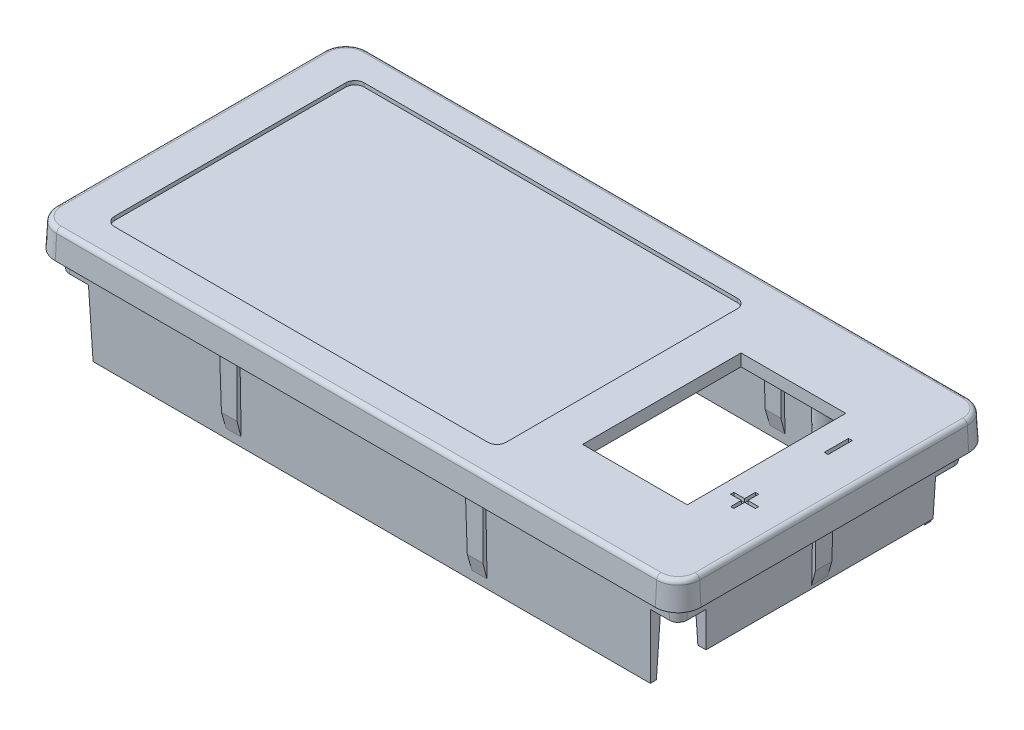
SolidWorks part; units mm, degrees
material "ABS PC"
ref_plane "Front" through (0, 0, 0) normal (0, 0, 1) x (1, 0, 0)
ref_plane "Top" through (0, 0, 0) normal (0, 1, 0) x (1, 0, 0)
ref_plane "Right" through (0, 0, 0) normal (1, 0, 0) x (0, 0, -1)
sketch "Sketch1" plane through (0, 0, 0) normal (0, 1, 0) x (1, 0, 0)
  line L1 (-32.95, -17.2) -> (32.95, -17.2)
  line L2 (-35.45, -14.7) -> (-35.45, 14.7)
  line L3 (-32.95, 17.2) -> (32.95, 17.2)
  line L4 (35.45, -14.7) -> (35.45, 14.7)
  line L5 (-35.45, -17.2) -> (35.45, 17.2) construction
  line L6 (-35.45, 17.2) -> (35.45, -17.2) construction
  arc A0 (32.95, -17.2) -> (35.45, -14.7) centre (32.95, -14.7) ccw
  arc A1 (-35.45, 14.7) -> (-32.95, 17.2) centre (-32.95, 14.7) cw
  arc A2 (-32.95, -17.2) -> (-35.45, -14.7) centre (-32.95, -14.7) cw
  arc A3 (32.95, 17.2) -> (35.45, 14.7) centre (32.95, 14.7) cw
  point P0 (0, 0)
  dimension "D3" = 2.5
  dimension "D1" = 70.9
  dimension "D2" = 34.4
extrude "Boss-Extrude1" add sketch "Sketch1" along normal blind 3 draft 3
fillet "Fillet1" radius 0.5 8 edges at (0, 3, 17.0428) (-34.6066, 3, 16.3566) (-35.2928, 3, 0) (-34.6066, 3, -16.3566) (0, 3, -17.0428) (34.6066, 3, -16.3566) (35.2928, 3, 0) (34.6066, 3, 16.3566)
sketch "Sketch2" plane through (0, 0, 0) normal (0, -1, 0) x (1, 0, 0)
  line L8 (32.95, 16.45) -> (-32.95, 16.45)
  line L9 (-34.7, 14.7) -> (-34.7, -14.7)
  line L10 (-32.95, -16.45) -> (32.95, -16.45)
  line L11 (34.7, -14.7) -> (34.7, 14.7)
  line L12 (32.95, 16.45) -> (-32.95, 16.45)
  line L13 (-34.7, 14.7) -> (-34.7, -14.7)
  line L14 (-32.95, -16.45) -> (32.95, -16.45)
  line L15 (34.7, -14.7) -> (34.7, 14.7)
  arc A8 (34.7, 14.7) -> (32.95, 16.45) centre (32.95, 14.7) ccw
  arc A9 (-32.95, 16.45) -> (-34.7, 14.7) centre (-32.95, 14.7) ccw
  arc A10 (-34.7, -14.7) -> (-32.95, -16.45) centre (-32.95, -14.7) ccw
  arc A11 (32.95, -16.45) -> (34.7, -14.7) centre (32.95, -14.7) ccw
  arc A12 (34.7, 14.7) -> (32.95, 16.45) centre (32.95, 14.7) ccw
  arc A13 (-32.95, 16.45) -> (-34.7, 14.7) centre (-32.95, 14.7) ccw
  arc A14 (-34.7, -14.7) -> (-32.95, -16.45) centre (-32.95, -14.7) ccw
  arc A15 (32.95, -16.45) -> (34.7, -14.7) centre (32.95, -14.7) ccw
  dimension "D1" = 0.75
extrude "Cut-Extrude1" cut sketch "Sketch2" against normal blind 0.5
sketch "Sketch4" plane through (0, 0.5, 0) normal (0, -1, 0) x (1, 0, 0)
  line L1 (31.65, -14.4) -> (-31.65, -14.4)
  line L2 (32.65, -13.4) -> (32.65, 13.4)
  line L3 (31.65, 14.4) -> (-31.65, 14.4)
  line L4 (-32.65, -13.4) -> (-32.65, 13.4)
  line L5 (32.65, -14.4) -> (-32.65, 14.4) construction
  line L6 (32.65, 14.4) -> (-32.65, -14.4) construction
  line L8 (32.95, 15.75) -> (-32.95, 15.75)
  line L9 (-34, 14.7) -> (-34, -14.7)
  line L10 (-32.95, -15.75) -> (32.95, -15.75)
  line L11 (34, -14.7) -> (34, 14.7)
  line L12 (32.95, 15.75) -> (-32.95, 15.75)
  line L13 (-34, 14.7) -> (-34, -14.7)
  line L14 (-32.95, -15.75) -> (32.95, -15.75)
  line L15 (34, -14.7) -> (34, 14.7)
  arc A0 (32.65, 13.4) -> (31.65, 14.4) centre (31.65, 13.4) ccw
  arc A1 (31.65, -14.4) -> (32.65, -13.4) centre (31.65, -13.4) ccw
  arc A2 (-31.65, -14.4) -> (-32.65, -13.4) centre (-31.65, -13.4) cw
  arc A3 (-31.65, 14.4) -> (-32.65, 13.4) centre (-31.65, 13.4) ccw
  arc A8 (34, 14.7) -> (32.95, 15.75) centre (32.95, 14.7) ccw
  arc A9 (-32.95, 15.75) -> (-34, 14.7) centre (-32.95, 14.7) ccw
  arc A10 (-34, -14.7) -> (-32.95, -15.75) centre (-32.95, -14.7) ccw
  arc A11 (32.95, -15.75) -> (34, -14.7) centre (32.95, -14.7) ccw
  arc A12 (34, 14.7) -> (32.95, 15.75) centre (32.95, 14.7) ccw
  arc A13 (-32.95, 15.75) -> (-34, 14.7) centre (-32.95, 14.7) ccw
  arc A14 (-34, -14.7) -> (-32.95, -15.75) centre (-32.95, -14.7) ccw
  arc A15 (32.95, -15.75) -> (34, -14.7) centre (32.95, -14.7) ccw
  point P0 (0, 0)
  dimension "D4" = 1
  dimension "D2" = 1.35
  dimension "D3" = 1.35
  dimension "D1" = 0.7
extrude "Boss-Extrude2" add sketch "Sketch4" along normal offset from surface 12.3 draft 2
sketch "Sketch5" plane through (0, 0.5, 0) normal (0, -1, 0) x (1, 0, 0)
  line L4 (31.65, 14.4) -> (-31.65, 14.4)
  line L5 (-32.65, 13.4) -> (-32.65, -13.4)
  line L6 (-31.65, -14.4) -> (31.65, -14.4)
  line L7 (32.65, -13.4) -> (32.65, 13.4)
  line L8 (31.65, 14.4) -> (-31.65, 14.4)
  line L9 (-32.65, 13.4) -> (-32.65, -13.4)
  line L10 (-31.65, -14.4) -> (31.65, -14.4)
  line L11 (32.65, -13.4) -> (32.65, 13.4)
  arc A4 (-31.65, 14.4) -> (-32.65, 13.4) centre (-31.65, 13.4) ccw
  arc A5 (-32.65, -13.4) -> (-31.65, -14.4) centre (-31.65, -13.4) ccw
  arc A6 (31.65, -14.4) -> (32.65, -13.4) centre (31.65, -13.4) ccw
  arc A7 (32.65, 13.4) -> (31.65, 14.4) centre (31.65, 13.4) ccw
  arc A8 (-31.65, 14.4) -> (-32.65, 13.4) centre (-31.65, 13.4) ccw
  arc A9 (-32.65, -13.4) -> (-31.65, -14.4) centre (-31.65, -13.4) ccw
  arc A10 (31.65, -14.4) -> (32.65, -13.4) centre (31.65, -13.4) ccw
  arc A11 (32.65, 13.4) -> (31.65, 14.4) centre (31.65, 13.4) ccw
  dimension "D1" = 0
extrude "Cut-Extrude2" cut sketch "Sketch5" against normal blind 1.2 draft 2
sketch "Sketch7" plane through (0, -9.3, 0) normal (0, -1, 0) x (1, 0, 0)
  line L1 (40, -13.25) -> (-40, -13.25)
  line L2 (40, -13.25) -> (40, 13.25)
  line L3 (40, 13.25) -> (-40, 13.25)
  line L4 (-40, -13.25) -> (-40, 13.25)
  line L5 (40, -13.25) -> (-40, 13.25) construction
  line L6 (40, 13.25) -> (-40, -13.25) construction
  point P0 (0, 0)
  dimension "D1" = 26.5
  dimension "D2" = 80
extrude "Cut-Extrude3" cut sketch "Sketch7" against normal offset from surface (3.3 mm away) 9 up to face at (0, 3, 0)
sketch "Sketch6" plane through (0, -9.3, 0) normal (0, -1, 0) x (1, 0, 0)
  line L0 (0, 25.2339) -> (0, -25.4955) construction
  line L1 (-36.3009, 18.0509) -> (-30.6, 18.0509)
  line L2 (-36.3009, 18.0509) -> (-36.3009, 12.35)
  line L3 (-36.3009, 12.35) -> (-30.6, 12.35)
  line L4 (-30.6, 18.0509) -> (-30.6, 12.35)
  line L5 (-36.3009, 18.0509) -> (-30.6, 12.35) construction
  line L6 (-36.3009, 12.35) -> (-30.6, 18.0509) construction
  line L7 (-41.5983, 0) -> (43.5606, 0) construction
  line L8 (36.3009, 12.35) -> (30.6, 18.0509) construction
  line L9 (36.3009, 18.0509) -> (30.6, 12.35) construction
  line L10 (30.6, 18.0509) -> (30.6, 12.35)
  line L11 (36.3009, 12.35) -> (30.6, 12.35)
  line L12 (36.3009, 18.0509) -> (36.3009, 12.35)
  line L13 (36.3009, 18.0509) -> (30.6, 18.0509)
  line L14 (36.3009, -18.0509) -> (30.6, -12.35) construction
  line L15 (36.3009, -12.35) -> (30.6, -18.0509) construction
  line L16 (-36.3009, -12.35) -> (-30.6, -18.0509) construction
  line L17 (-36.3009, -18.0509) -> (-30.6, -12.35) construction
  line L18 (36.3009, -18.0509) -> (30.6, -18.0509)
  line L19 (36.3009, -18.0509) -> (36.3009, -12.35)
  line L20 (36.3009, -12.35) -> (30.6, -12.35)
  line L21 (30.6, -18.0509) -> (30.6, -12.35)
  line L22 (-30.6, -18.0509) -> (-30.6, -12.35)
  line L23 (-36.3009, -12.35) -> (-30.6, -12.35)
  line L24 (-36.3009, -18.0509) -> (-36.3009, -12.35)
  line L25 (-36.3009, -18.0509) -> (-30.6, -18.0509)
  arc A0 (-32.95, 15.4078) -> (-33.6578, 14.7) centre (-32.95, 14.7) ccw construction
  point P0 (-33.4505, 15.2005)
  point P14 (33.4505, 15.2005)
  point P23 (33.4505, -15.2005)
  point P24 (-33.4505, -15.2005)
  dimension "D1" = 61.2
extrude "Cut-Extrude4" cut sketch "Sketch6" against normal offset from surface 5 draft 2
sketch "Sketch8" plane through (0, -9.3, 0) normal (0, -1, 0) x (1, 0, 0)
  line L0 (-30.6, -15.4078) -> (-30.6, -14.7422) construction
  line L1 (-26.8, -14.0722) -> (5.2, -14.0722)
  line L2 (-26.8, -14.0722) -> (-26.8, -16.0722)
  line L3 (-26.8, -16.0722) -> (5.2, -16.0722)
  line L4 (5.2, -14.0722) -> (5.2, -16.0722)
  line L5 (-26.8, -14.0722) -> (5.2, -16.0722) construction
  line L6 (-26.8, -16.0722) -> (5.2, -14.0722) construction
  line L8 (30.6, -14.7422) -> (-30.6, -14.7422) construction
  point P0 (-10.8, -15.0722)
  dimension "D1" = 3.8
  dimension "D2" = 32
  dimension "D3" = 2
  dimension "D4" = 0.33
extrude "Cut-Extrude5" cut sketch "Sketch8" against normal up to surface (7.3 mm away) up to face at (-32.5043, -2, -14.2543)
fillet "Fillet3" radius 0.5 8 edges at (32.3275, 1.7, 14.0775) (32.6081, 1.7, 0) (32.3275, 1.7, -14.0775) (0, 1.7, -14.3581) (-32.3275, 1.7, -14.0775) (-32.6081, 1.7, 0) (-32.3275, 1.7, 14.0775) (0, 1.7, 14.3581)
sketch "Sketch9" plane through (0, 1.7, 0) normal (0, -1, 0) x (1, 0, 0)
  line L0 (-32.1253, 13.4) -> (-32.1253, -13.4) construction
  line L2 (31.65, 13.8753) -> (-31.65, 13.8753) construction
  line L3 (0, 20.8963) -> (0, -22.9898) construction
  line L4 (48.011, 0) -> (-42.4283, 0) construction
  circle A0 centre (-30.6253, 12.3753) radius 1.5
  circle A4 centre (-30.6253, 12.3753) radius 0.8
  circle A5 centre (30.6253, 12.3753) radius 0.8
  circle A6 centre (30.6253, 12.3753) radius 1.5
  circle A7 centre (30.6253, -12.3753) radius 1.5
  circle A8 centre (30.6253, -12.3753) radius 0.8
  circle A9 centre (-30.6253, -12.3753) radius 0.8
  circle A10 centre (-30.6253, -12.3753) radius 1.5
  dimension "D1" = 3
  dimension "D2" = 1.5
  dimension "D3" = 1.5
  dimension "D4" = 0.7
extrude "Boss-Extrude3" add sketch "Sketch9" along normal blind 0.6 draft 2
sketch "Sketch10" plane through (0, 1.7, 0) normal (0, -1, 0) x (1, 0, 0)
  line L0 (-32.877, 0) -> (32.877, 0) construction
  line L1 (-32.877, -12.4652) -> (-32.877, 12.4652) construction
  line L2 (32.877, 12.4652) -> (32.877, -12.4652) construction
  line L3 (35.45, 14.7) -> (35.45, -14.7) construction
  line L4 (-31.65, 14.3749) -> (31.65, 14.3749) construction
  line L5 (-32.6249, -13.4) -> (-32.6249, 13.4) construction
  circle A0 centre (21.95, 12.6249) radius 1.75
  circle A1 centre (21.95, -12.6249) radius 1.75
  circle A2 centre (-30.8749, 0) radius 1.75
  dimension "D2" = 3.5
  dimension "D4" = 1.75
  dimension "D1" = 13.5
  dimension "D3" = 1.75
extrude "Boss-Extrude4" add sketch "Sketch10" along normal blind 1 draft 2
sketch "Sketch11" plane through (0, 1.7, 0) normal (0, -1, 0) x (1, 0, 0)
  line L0 (35.45, 0) -> (-35.45, 0) construction
  line L1 (35.45, 14.7) -> (35.45, -14.7) construction
  line L2 (-35.45, -14.7) -> (-35.45, 14.7) construction
  circle A0 centre (21.95, 12.6249) radius 1.25
  circle A1 centre (21.95, 12.6249) radius 0.55
  circle A2 centre (21.95, -12.6249) radius 0.55
  circle A3 centre (21.95, -12.6249) radius 1.25
  circle A4 centre (-30.8749, 0) radius 1.25
  circle A5 centre (-30.8749, 0) radius 0.55
  dimension "D1" = 2.5
  dimension "D2" = 0.7
extrude "Boss-Extrude5" add sketch "Sketch11" along normal blind 6 draft 1
sketch "Sketch12" plane through (0, 3, 0) normal (0, 1, 0) x (1, 0, 0)
  line L0 (35.45, -14.7) -> (35.45, 14.7) construction
  line L1 (16.45, -8.7) -> (27.95, -8.7)
  line L2 (16.45, -8.7) -> (16.45, 8.7)
  line L3 (16.45, 8.7) -> (27.95, 8.7)
  line L4 (27.95, -8.7) -> (27.95, 8.7)
  line L5 (16.45, -8.7) -> (27.95, 8.7) construction
  line L6 (16.45, 8.7) -> (27.95, -8.7) construction
  line L9 (-32.95, -17.2) -> (32.95, -17.2) construction
  line L11 (32.95, 17.2) -> (-32.95, 17.2) construction
  point P0 (22.2, 0)
  dimension "D1" = 7.5
  dimension "D2" = 8.5
  dimension "D3" = 8.5
  dimension "D4" = 11.5
extrude "Cut-Extrude6" cut sketch "Sketch12" against normal through all draft 1
sketch "Sketch13" plane through (0, 3, 0) normal (0, 1, 0) x (1, 0, 0)
  line L0 (-35.45, 14.7) -> (-35.45, -14.7) construction
  line L1 (-29.95, -13.7) -> (11.05, -13.7)
  line L2 (-30.95, -12.7) -> (-30.95, 12.7)
  line L3 (-29.95, 13.7) -> (11.05, 13.7)
  line L4 (12.05, -12.7) -> (12.05, 12.7)
  line L5 (-30.95, -13.7) -> (12.05, 13.7) construction
  line L6 (-30.95, 13.7) -> (12.05, -13.7) construction
  line L7 (32.95, 17.2) -> (-32.95, 17.2) construction
  arc A0 (11.05, -13.7) -> (12.05, -12.7) centre (11.05, -12.7) ccw
  arc A1 (-30.95, 12.7) -> (-29.95, 13.7) centre (-29.95, 12.7) cw
  arc A2 (-29.95, -13.7) -> (-30.95, -12.7) centre (-29.95, -12.7) cw
  arc A3 (11.05, 13.7) -> (12.05, 12.7) centre (11.05, 12.7) cw
  point P0 (-9.45, 0)
  dimension "D4" = 1
  dimension "D1" = 4.5
  dimension "D2" = 3.5
  dimension "D3" = 43
extrude "Cut-Extrude7" cut sketch "Sketch13" against normal blind 0.4 draft 2
sketch "Sketch14" plane through (0, 3, 0) normal (0, 1, 0) x (1, 0, 0)
  line L0 (32.2274, 6.7344) -> (32.2274, 3.8531) construction
  line L1 (32.6557, -3.4671) -> (32.6557, -8.7237) construction
  text T0 "+" font "Century Gothic" height 4
  text T1 "-" font "Century Gothic" height 4
extrude "Cut-Extrude8" cut sketch "Sketch14" against normal blind 0.4 draft 1
sketch "Sketch16" plane through (0, 1.7, 0) normal (0, -1, 0) x (1, 0, 0)
  line L0 (-32.1253, 12.3753) -> (-32.1253, 1.2244) construction
  line L1 (-16.1253, 14.075) -> (-14.1253, 14.075)
  line L2 (-16.1253, 14.075) -> (-16.1253, 16.075)
  line L3 (-16.1253, 16.075) -> (-14.1253, 16.075)
  line L4 (-14.1253, 14.075) -> (-14.1253, 16.075)
  line L5 (-16.1253, 15.075) -> (-30.6, 15.075) construction
  line L6 (-30.6, 14.7422) -> (-30.6, 15.4078) construction
  line L7 (10.8747, 14.075) -> (12.8747, 14.075)
  line L8 (10.8747, 14.075) -> (10.8747, 16.075)
  line L9 (10.8747, 16.075) -> (12.8747, 16.075)
  line L10 (12.8747, 14.075) -> (12.8747, 16.075)
  line L11 (5.2, -15.075) -> (14.45, -15.075) construction
  line L12 (13.45, -16.075) -> (15.45, -16.075)
  line L13 (13.45, -16.075) -> (13.45, -14.075)
  line L14 (13.45, -14.075) -> (15.45, -14.075)
  line L15 (15.45, -16.075) -> (15.45, -14.075)
  line L16 (13.45, -16.075) -> (15.45, -14.075) construction
  line L17 (13.45, -14.075) -> (15.45, -16.075) construction
  line L18 (5.2, -15.4078) -> (5.2, -14.7422) construction
  line L19 (35.45, 14.7) -> (35.45, -14.7) construction
  line L20 (-30.6, -15.075) -> (-26.8, -15.075) construction
  line L21 (-30.6, -15.4078) -> (-30.6, -14.7422) construction
  line L22 (-26.8, -14.4873) -> (-26.8, -15.6627) construction
  line L23 (-28.7, -14.7422) -> (-28.7, -15.4078) construction
  line L24 (-26.8, -14.7422) -> (-30.6, -14.7422) construction
  line L25 (-26.8, -15.4078) -> (-30.6, -15.4078) construction
  line L27 (-29.7, -16.075) -> (-27.7, -16.075)
  line L28 (-29.7, -16.075) -> (-29.7, -14.075)
  line L29 (-29.7, -14.075) -> (-27.7, -14.075)
  line L30 (-27.7, -16.075) -> (-27.7, -14.075)
  line L31 (-29.7, -16.075) -> (-27.7, -14.075) construction
  line L32 (-29.7, -14.075) -> (-27.7, -16.075) construction
  point P10 (14.45, -15.075)
  point P37 (-28.7, -15.075)
  dimension "D1" = 16
  dimension "D2" = 2
  dimension "D4" = 2
  dimension "D7" = 20
extrude "Boss-Extrude7" add sketch "Sketch16" along normal blind 10 draft 1
sketch "Sketch17" plane through (0, 1.7, 0) normal (0, -1, 0) x (1, 0, 0)
  line L0 (33.325, 12.4652) -> (33.325, -12.4652) construction
  line L1 (33.325, -1) -> (34.325, -1)
  line L2 (33.325, -1) -> (33.325, 1)
  line L3 (33.325, 1) -> (34.325, 1)
  line L4 (34.325, -1) -> (34.325, 1)
  line L5 (33.773, 12.4652) -> (32.877, 12.4652) construction
  line L6 (32.877, -12.4652) -> (33.773, -12.4652) construction
  line L7 (-33.325, 12.4652) -> (-33.325, -12.4652) construction
  line L8 (-32.877, 12.4652) -> (-33.773, 12.4652) construction
  line L9 (-33.773, -12.4652) -> (-32.877, -12.4652) construction
  line L10 (33.325, 0) -> (32.877, 0) construction
  line L11 (32.877, 12.4652) -> (32.877, -12.4652) construction
  line L12 (-32.95, 17.2) -> (32.95, 17.2) construction
  line L13 (-33.325, 9.2) -> (-34.325, 9.2)
  line L14 (-33.325, 9.2) -> (-33.325, 7.2)
  line L15 (-33.325, 7.2) -> (-34.325, 7.2)
  line L16 (-34.325, 9.2) -> (-34.325, 7.2)
  line L17 (-33.325, -4.8) -> (-34.325, -4.8)
  line L18 (-33.325, -4.8) -> (-33.325, -6.8)
  line L19 (-33.325, -6.8) -> (-34.325, -6.8)
  line L20 (-34.325, -4.8) -> (-34.325, -6.8)
  dimension "D1" = 1
  dimension "D2" = 2
  dimension "D3" = 8
  dimension "D4" = 2
extrude "Boss-Extrude8" add sketch "Sketch17" along normal blind 7.5 draft 1
chamfer "Chamfer1" distance 1.75 distance2 0.45 11 edges at (-15.1253, -8.3, 14.2496) (-15.1253, -8.3, 15.9004) (-28.7, -8.3, -14.2496) (-28.7, -8.3, -15.9004) (14.45, -8.3, -15.9004) (14.45, -8.3, -14.2496) (11.8747, -8.3, 15.9004) (11.8747, -8.3, 14.2496) (34.1941, -5.8, 0) (-34.1941, -5.8, 8.2) (-34.1941, -5.8, -5.8)
